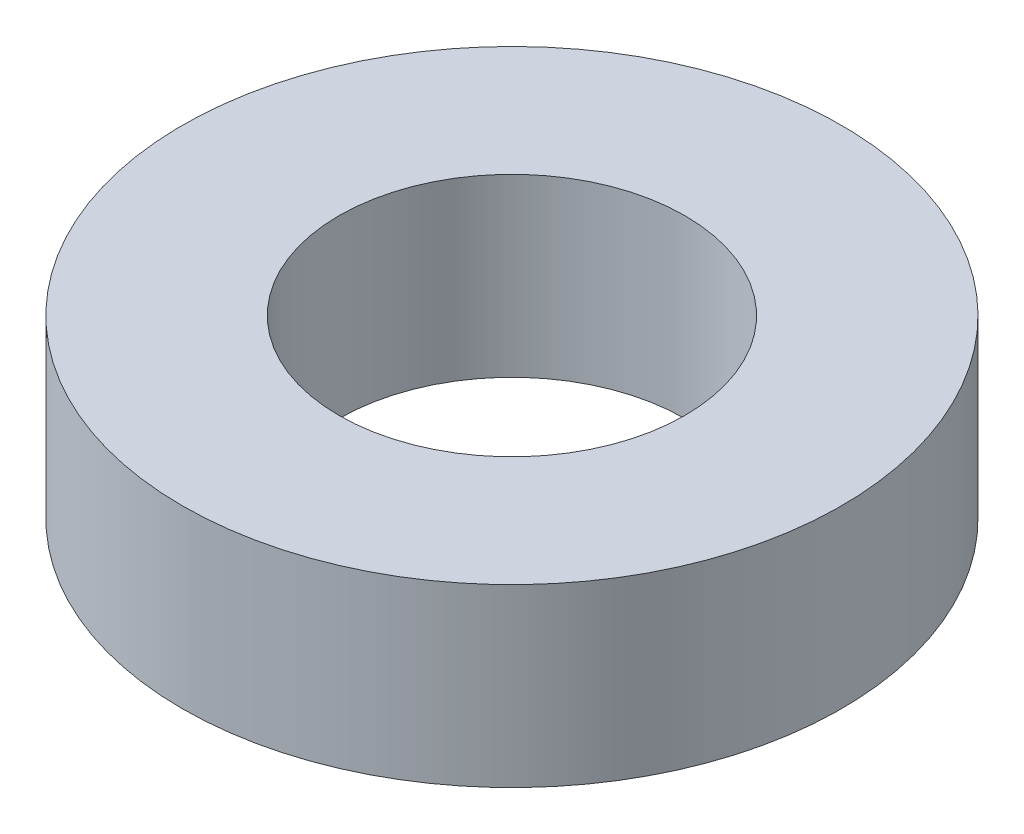
SolidWorks part; units mm, degrees
ref_plane "Front Plane" through (0, 0, 0) normal (0, 0, 1) x (1, 0, 0)
ref_plane "Top Plane" through (0, 0, 0) normal (0, 1, 0) x (1, 0, 0)
ref_plane "Right Plane" through (0, 0, 0) normal (1, 0, 0) x (0, 0, -1)
sketch "Sketch1" plane through (0, 0, 0) normal (0, 1, 0) x (1, 0, 0)
  circle A0 centre (0, 0) radius 2.5
  circle A1 centre (0, 0) radius 4.7625
  dimension "D1" = 5
  dimension "D2" = 9.525
extrude "Boss-Extrude1" add sketch "Sketch1" along normal blind 2.54
